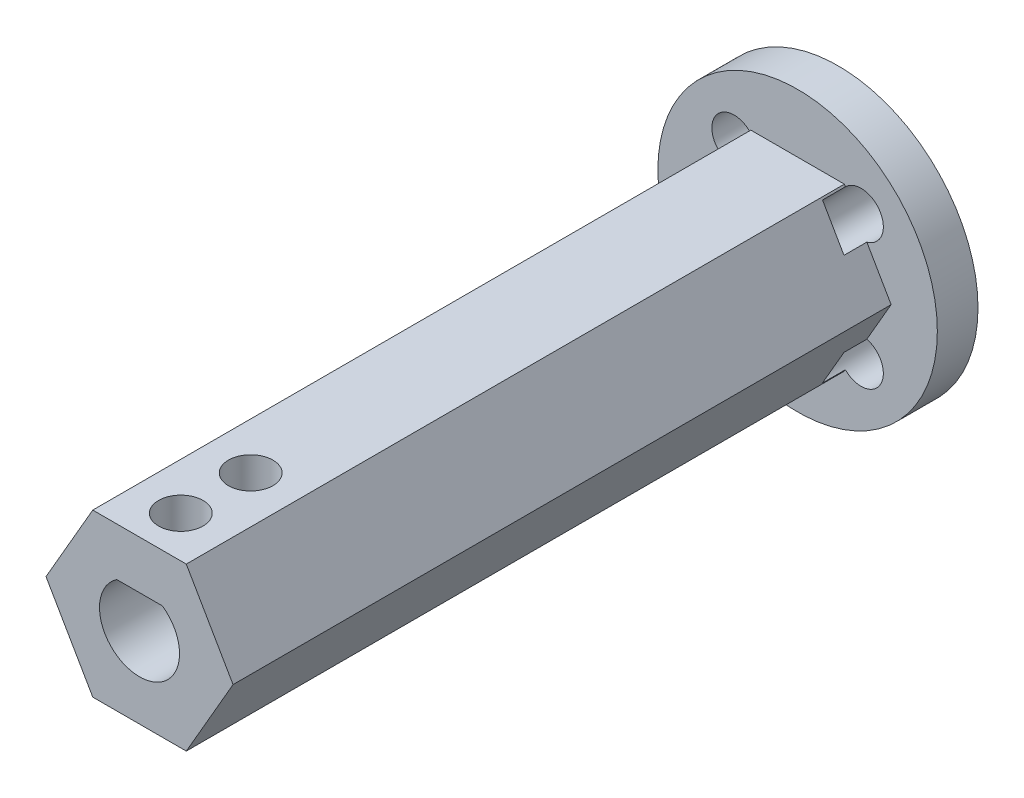
SolidWorks part; units mm, degrees
ref_plane "Alzado" through (0, 0, 0) normal (0, 0, 1) x (1, 0, 0)
ref_plane "Planta" through (0, 0, 0) normal (0, 1, 0) x (1, 0, 0)
ref_plane "Vista lateral" through (0, 0, 0) normal (1, 0, 0) x (0, 0, -1)
sketch "Croquis1" plane through (0, 0, 0) normal (0, 0, 1) x (1, 0, 0)
  line L0 (0, 0) -> (0, 2.5851) construction
  line L1 (7.3617, 0) -> (3.6808, 6.3754)
  line L2 (3.6808, 6.3754) -> (-3.6808, 6.3754)
  line L3 (-3.6808, 6.3754) -> (-7.3617, 0)
  line L4 (-7.3617, 0) -> (-3.6808, -6.3754)
  line L5 (-3.6808, -6.3754) -> (3.6808, -6.3754)
  line L6 (3.6808, -6.3754) -> (7.3617, 0)
  line L7 (-1.8, 2.5851) -> (1.8, 2.5851)
  circle A0 centre (0, 0) radius 6.3754 construction
  arc A1 (-1.8, 2.5851) -> (1.8, 2.5851) centre (0, 0) ccw
  point P14 (0, 2.5851)
  dimension "D2" = 6.3
  dimension "D1" = 12.7508
  dimension "D3" = 3.6
extrude "Saliente-Extruir1" add sketch "Croquis1" along normal blind 55
sketch "Croquis2" plane through (0, 6.3754, 0) normal (0, 1, 0) x (1, 0, 0)
  line L0 (0, -55) -> (0, -51.75) construction
  line L1 (3.6808, -55) -> (-3.6808, -55) construction
  line L2 (0, -51.75) -> (0, -50) construction
  line L3 (0, -50) -> (0, -48) construction
  line L4 (0, -48) -> (0, -46.25) construction
  line L5 (0, -46.25) -> (0, -43) construction
  circle A0 centre (0, -51.75) radius 1.75
  circle A1 centre (0, -46.25) radius 1.75
  dimension "D1" = 3.5
  dimension "D2" = 12
  dimension "D3" = 2
extrude "Cortar-Extruir1" cut sketch "Croquis2" against normal blind 7.5
sketch "Croquis3" plane through (0, 0, 0) normal (0, 0, -1) x (-1, 0, 0)
  circle A0 centre (0, 0) radius 11
  dimension "D1" = 22
extrude "Saliente-Extruir2" add sketch "Croquis3" against normal blind 3.2
sketch "Croquis5" plane through (0, 0, 0) normal (0, 0, -1) x (-1, 0, 0)
  line L0 (0, 0) -> (0, 5) construction
  line L1 (0, 5) -> (-5, 5) construction
  circle A0 centre (-5, 5) radius 1.75
  circle A1 centre (5, 5) radius 1.75
  circle A2 centre (5, -5) radius 1.75
  circle A3 centre (-5, -5) radius 1.75
  point P14 (0, 0)
  dimension "D3" = 3.5
  dimension "D1" = 5
  dimension "D2" = 5
  dimension "D5" = 10
  dimension "D4" = 4
extrude "Cortar-Extruir2" cut sketch "Croquis5" against normal blind 5 and the other way through all
